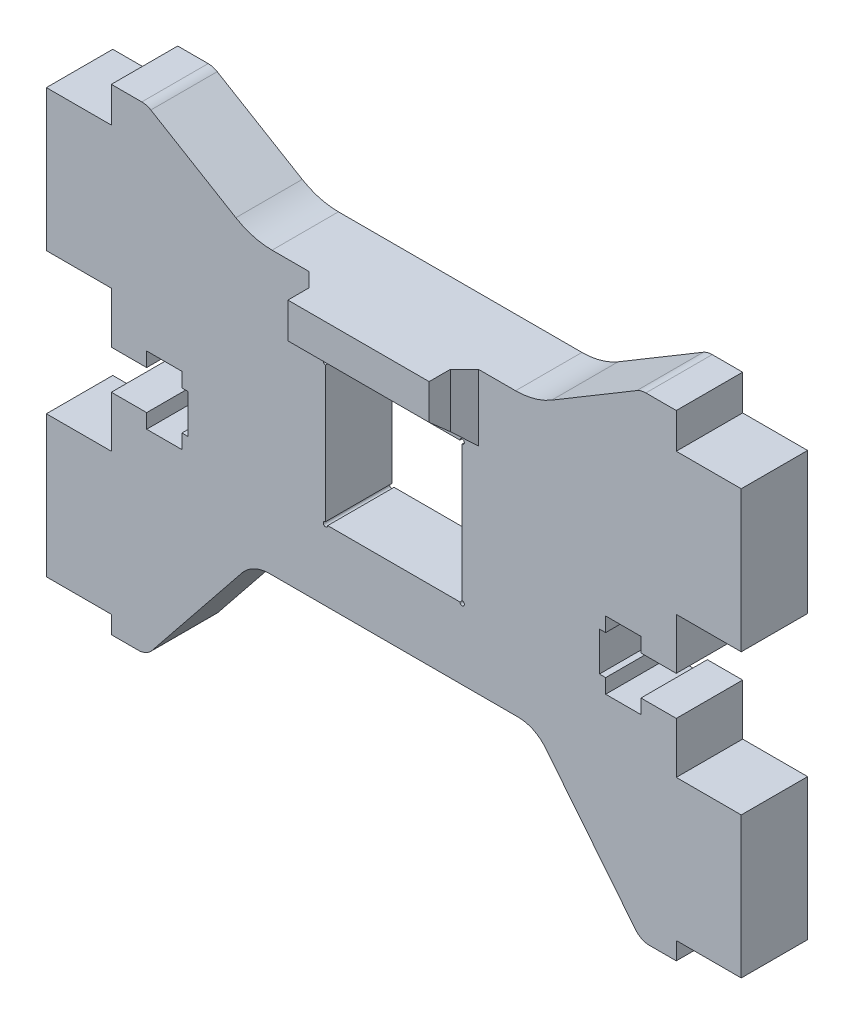
SolidWorks part; units mm, degrees
ref_plane "Front Plane" through (0, 0, 0) normal (0, 0, 1) x (1, 0, 0)
ref_plane "Top Plane" through (0, 0, 0) normal (0, 1, 0) x (1, 0, 0)
ref_plane "Right Plane" through (0, 0, 0) normal (1, 0, 0) x (0, 0, -1)
sketch "Sketch1" plane through (0, 0, 0) normal (0, 0, 1) x (1, 0, 0)
  line L0 (0, 0) -> (0, -22.937) construction
  line L1 (6.1452, -6.3) -> (-6.1452, -6.3)
  line L2 (6.1452, -6.3) -> (6.1452, 6.3)
  line L3 (6.1452, 6.3) -> (-6.1452, 6.3)
  line L4 (-6.1452, -6.3) -> (-6.1452, 6.3)
  line L5 (6.1452, -6.3) -> (-6.1452, 6.3) construction
  line L6 (6.1452, 6.3) -> (-6.1452, -6.3) construction
  line L7 (25.4, -22.937) -> (-25.4, -22.937) construction
  line L8 (25.4, 2.463) -> (25.4, -10.237)
  line L9 (25.4, -22.937) -> (31.242, -22.937)
  line L10 (-31.242, 2.463) -> (-25.4, 2.463)
  line L11 (31.242, -10.237) -> (25.4, -10.237)
  line L12 (31.242, -22.937) -> (31.242, -10.237)
  line L13 (25.4, -22.937) -> (25.4, -24.5245)
  line L14 (-12.7, -12.65) -> (12.7, -12.65)
  line L15 (12.7, -12.65) -> (22.225, -24.5245)
  line L16 (22.225, -24.5245) -> (25.4, -24.5245)
  line L17 (-12.7, 12.65) -> (12.7, 12.65)
  line L18 (-12.7, 12.65) -> (-22.225, 18.338)
  line L19 (-31.242, -10.237) -> (-25.4, -10.237)
  line L20 (-31.242, -22.937) -> (-31.242, -10.237)
  line L21 (-25.4, -22.937) -> (-31.242, -22.937)
  line L22 (-25.4, -22.937) -> (-25.4, -24.5245)
  line L23 (-22.225, -24.5245) -> (-25.4, -24.5245)
  line L24 (-12.7, -12.65) -> (-22.225, -24.5245)
  line L25 (-25.4, 18.338) -> (-22.225, 18.338)
  line L26 (-25.4, 2.463) -> (-25.4, -10.237)
  line L27 (31.242, 2.463) -> (25.4, 2.463)
  line L28 (31.242, 2.463) -> (31.242, 15.163)
  line L29 (31.242, 15.163) -> (25.4, 15.163)
  line L30 (25.4, 15.163) -> (25.4, 18.338)
  line L31 (25.4, 18.338) -> (22.225, 18.338)
  line L32 (-25.4, 15.163) -> (-25.4, 18.338)
  line L33 (12.7, 12.65) -> (22.225, 18.338)
  line L34 (-31.242, 15.163) -> (-25.4, 15.163)
  line L35 (-31.242, 2.463) -> (-31.242, 15.163)
  point P0 (0, 0)
  point P11 (0, -22.937)
  point P28 (0, -12.65)
  point P29 (0, 12.65)
  dimension "D1" = 12.6
  dimension "D2" = 12.2904
  dimension "D3" = 16.637
  dimension "D4" = 50.8
  dimension "D5" = 12.7
  dimension "D6" = 5.842
  dimension "D7" = 12.7
  dimension "D8" = 1.5875
  dimension "D9" = 12.7
  dimension "D10" = 6.35
  dimension "D11" = 3.175
  dimension "D12" = 6.35
  dimension "D13" = 12.7
  dimension "D16" = 12.7
  dimension "D17" = 3.175
  dimension "D18" = 3.175
extrude "Boss-Extrude1" add sketch "Sketch1" along normal blind 5.969
sketch "Sketch2" plane through (0, 0, 5.969) normal (0, 0, 1) x (1, 0, 0)
  line L0 (-25.4, -3.887) -> (25.4, -3.887) construction
  line L1 (-25.4, 2.463) -> (-25.4, -10.237) construction
  line L2 (25.4, -10.237) -> (25.4, 2.463) construction
  line L3 (22.225, -2.1344) -> (22.225, -0.839)
  line L4 (22.225, -5.6396) -> (25.4, -5.6396)
  line L5 (0, -3.887) -> (0, -12.65) construction
  line L6 (22.225, -2.1344) -> (25.4, -2.1344)
  line L7 (25.4, -5.6396) -> (25.4, -2.1344)
  line L8 (22.225, -5.6396) -> (25.4, -2.1344) construction
  line L9 (22.225, -2.1344) -> (25.4, -5.6396) construction
  line L10 (19.05, -6.935) -> (22.225, -6.935)
  line L11 (19.05, -6.935) -> (19.05, -5.6396)
  line L12 (19.05, -0.839) -> (22.225, -0.839)
  line L13 (22.225, -6.935) -> (22.225, -5.6396)
  line L14 (19.05, -6.935) -> (22.225, -0.839) construction
  line L15 (19.05, -0.839) -> (22.225, -6.935) construction
  line L16 (18.492, -5.6396) -> (19.05, -5.6396)
  line L17 (18.492, -5.6396) -> (18.492, -2.1344)
  line L18 (18.492, -2.1344) -> (19.05, -2.1344)
  line L19 (-12.7, -12.65) -> (12.7, -12.65) construction
  line L20 (18.492, -5.6396) -> (19.05, -2.1344) construction
  line L21 (18.492, -2.1344) -> (19.05, -5.6396) construction
  line L22 (19.05, -2.1344) -> (19.05, -0.839)
  line L23 (-18.492, -2.1344) -> (-19.05, -5.6396) construction
  line L24 (-18.492, -5.6396) -> (-19.05, -2.1344) construction
  line L25 (-19.05, -0.839) -> (-22.225, -6.935) construction
  line L26 (-19.05, -6.935) -> (-22.225, -0.839) construction
  line L27 (-22.225, -2.1344) -> (-25.4, -5.6396) construction
  line L28 (-22.225, -5.6396) -> (-25.4, -2.1344) construction
  line L29 (-19.05, -2.1344) -> (-19.05, -0.839)
  line L30 (-18.492, -2.1344) -> (-19.05, -2.1344)
  line L31 (-18.492, -5.6396) -> (-18.492, -2.1344)
  line L32 (-18.492, -5.6396) -> (-19.05, -5.6396)
  line L33 (-22.225, -6.935) -> (-22.225, -5.6396)
  line L34 (-19.05, -0.839) -> (-22.225, -0.839)
  line L35 (-19.05, -6.935) -> (-19.05, -5.6396)
  line L36 (-19.05, -6.935) -> (-22.225, -6.935)
  line L37 (-25.4, -5.6396) -> (-25.4, -2.1344)
  line L38 (-22.225, -2.1344) -> (-25.4, -2.1344)
  line L39 (-22.225, -5.6396) -> (-25.4, -5.6396)
  line L40 (-22.225, -2.1344) -> (-22.225, -0.839)
  point P6 (23.8125, -3.887)
  point P11 (20.6375, -3.887)
  point P16 (18.771, -3.887)
  point P37 (-18.771, -3.887)
  point P38 (-20.6375, -3.887)
  point P39 (-23.8125, -3.887)
  dimension "D1" = 3.175
  dimension "D2" = 3.175
  dimension "D3" = 3.5052
  dimension "D4" = 6.096
  dimension "D5" = 0.558
extrude "Cut-Extrude1" cut sketch "Sketch2" against normal through all
sketch "Sketch3" plane through (0, 0, 5.969) normal (0, 0, 1) x (1, 0, 0)
  line L0 (-6.1452, 0) -> (6.1452, 0) construction
  line L1 (-6.1452, 6.3) -> (-6.1452, -6.3) construction
  line L2 (6.1452, -6.3) -> (6.1452, 6.3) construction
  circle A0 centre (6.1452, 6.3) radius 0.1984
  circle A1 centre (-6.1452, 6.3) radius 0.1984
  circle A2 centre (-6.1452, -6.3) radius 0.1984
  circle A3 centre (6.1452, -6.3) radius 0.1984
  dimension "D1" = 0.3969
  dimension "D2" = 0.3969
extrude "Cut-Extrude2" cut sketch "Sketch3" against normal through all
fillet "Fillet1" radius 3.175 2 edges at (-12.7, -12.65, 2.9845) (12.7, -12.65, 2.9845)
fillet "Fillet2" radius 1.5875 4 edges at (22.225, -24.5245, 2.9845) (-22.225, -24.5245, 2.9845) (-22.225, 18.338, 2.9845) (22.225, 18.338, 2.9845)
sketch "Sketch4" plane through (0, 0, 5.969) normal (0, 0, 1) x (1, 0, 0)
  line L0 (-6.1452, 0) -> (6.1452, 0) construction
  line L1 (-6.1452, 6.1016) -> (-6.1452, -6.1016) construction
  line L2 (6.1452, -6.1016) -> (6.1452, 6.1016) construction
  line L4 (6.35, -5.5562) -> (-6.35, -5.5563)
  line L5 (6.35, -5.5562) -> (6.35, 5.5563)
  line L6 (6.35, 5.5563) -> (-6.35, 5.5562)
  line L7 (-6.35, -5.5563) -> (-6.35, 5.5562)
  line L8 (6.35, -5.5562) -> (-6.35, 5.5562) construction
  line L9 (6.35, 5.5563) -> (-6.35, -5.5563) construction
  point P6 (0, 0)
  dimension "D1" = 12.7
  dimension "D2" = 11.1125
extrude "Cut-Extrude3" [suppressed] cut sketch "Sketch4" against normal through all
fillet "Fillet7" [suppressed] radius 0.1
sketch "Sketch5" plane through (0, 0, 5.969) normal (0, 0, 1) x (1, 0, 0)
  line L0 (5.9468, 6.3) -> (-5.9468, 6.3) construction
  line L1 (5.08, 6.05) -> (-5.08, 6.05)
  line L2 (5.08, 6.05) -> (5.08, 6.55)
  line L3 (5.08, 6.55) -> (-5.08, 6.55)
  line L4 (-5.08, 6.05) -> (-5.08, 6.55)
  line L5 (5.08, 6.05) -> (-5.08, 6.55) construction
  line L6 (5.08, 6.55) -> (-5.08, 6.05) construction
  point P0 (0, 6.3)
  dimension "D1" = 10.16
  dimension "D2" = 0.5
extrude "Cut-Extrude4" [suppressed] cut sketch "Sketch5" against normal through all
fillet "Fillet8" [suppressed] radius 0.1
sketch "Sketch6" plane through (0, 0, 5.969) normal (0, 0, 1) x (1, 0, 0)
  line L0 (-12.7, 12.65) -> (-12.7, -12.65) construction
  line L1 (12.7, 12.65) -> (-12.7, 12.65) construction
  line L2 (-11.1766, -12.65) -> (11.1766, -12.65) construction
  line L3 (-15.7, 6.3) -> (-9.7, 6.3) construction
  line L4 (-15.7, 7.3) -> (-9.7, 7.3)
  line L5 (-15.7, 5.3) -> (-9.7, 5.3)
  line L6 (-15.7, -0.05) -> (-9.7, -0.05) construction
  line L7 (-15.7, 0.95) -> (-9.7, 0.95)
  line L8 (-15.7, -1.05) -> (-9.7, -1.05)
  arc A0 (-15.7, 7.3) -> (-15.7, 5.3) centre (-15.7, 6.3) ccw
  arc A1 (-9.7, 5.3) -> (-9.7, 7.3) centre (-9.7, 6.3) ccw
  arc A2 (-15.7, 0.95) -> (-15.7, -1.05) centre (-15.7, -0.05) ccw
  arc A3 (-9.7, -1.05) -> (-9.7, 0.95) centre (-9.7, -0.05) ccw
  point P8 (-12.7, 6.3)
  point P17 (-12.7, -0.05)
  point P18 (-12.7, -2.413)
  dimension "D2" = 1
  dimension "D1" = 6
  dimension "D3" = 12.7
  dimension "D5" = 6.35
extrude "Cut-Extrude5" [suppressed] cut sketch "Sketch6" against normal through all
fillet "Fillet9" radius 6.35 2 edges at (12.7, 12.65, 2.9845) (-12.7, 12.65, 2.9845)
sketch "Sketch7" plane through (0, 0, 5.969) normal (0, 0, 1) x (1, 0, 0)
  line L0 (0, 12.65) -> (0, -12.65) construction
  line L1 (10.9483, 12.65) -> (-10.9483, 12.65) construction
  line L2 (-11.1766, -12.65) -> (11.1766, -12.65) construction
  line L4 (6.35, 9.475) -> (-6.35, 9.475)
  line L5 (6.35, 9.475) -> (6.35, 12.65)
  line L6 (6.35, 12.65) -> (-6.35, 12.65)
  line L7 (-6.35, 9.475) -> (-6.35, 12.65)
  line L8 (6.35, 9.475) -> (-6.35, 12.65) construction
  line L9 (6.35, 12.65) -> (-6.35, 9.475) construction
  point P6 (0, 11.0625)
  dimension "D1" = 12.7
  dimension "D2" = 3.175
extrude "Boss-Extrude2" add sketch "Sketch7" along normal blind 3.175
sketch "Sketch8" plane through (-6.35, 0, 0) normal (-1, 0, 0) x (0, 0, 1)
  line L0 (5.969, 9.475) -> (5.969, 6.681)
  line L1 (5.969, 6.681) -> (9.144, 9.475)
  line L2 (9.144, 9.475) -> (5.969, 9.475) construction
  line L3 (9.144, 9.475) -> (5.969, 9.475)
  dimension "D1" = 2.794
extrude "Boss-Extrude3" add sketch "Sketch8" against normal blind 3.175
sketch "Sketch9" plane through (0, 0, 9.144) normal (0, 0, 1) x (1, 0, 0)
  line L0 (0, 12.65) -> (0, 9.475) construction
  line L1 (6.35, 12.65) -> (-6.35, 12.65) construction
  line L2 (-3.175, 9.475) -> (6.35, 9.475) construction
ref_plane "Plane1" through (0, 0, 0) normal (1, 0, 0) x (0, 0, -1)
mirror "Mirror1" about plane through (0, 0, 0) normal (1, 0, 0) of "Boss-Extrude3"
chamfer "Chamfer1" distance 1.27 angle 45 2 edges at (-6.35, 9.6655, 5.969) (6.35, 9.6655, 5.969)
